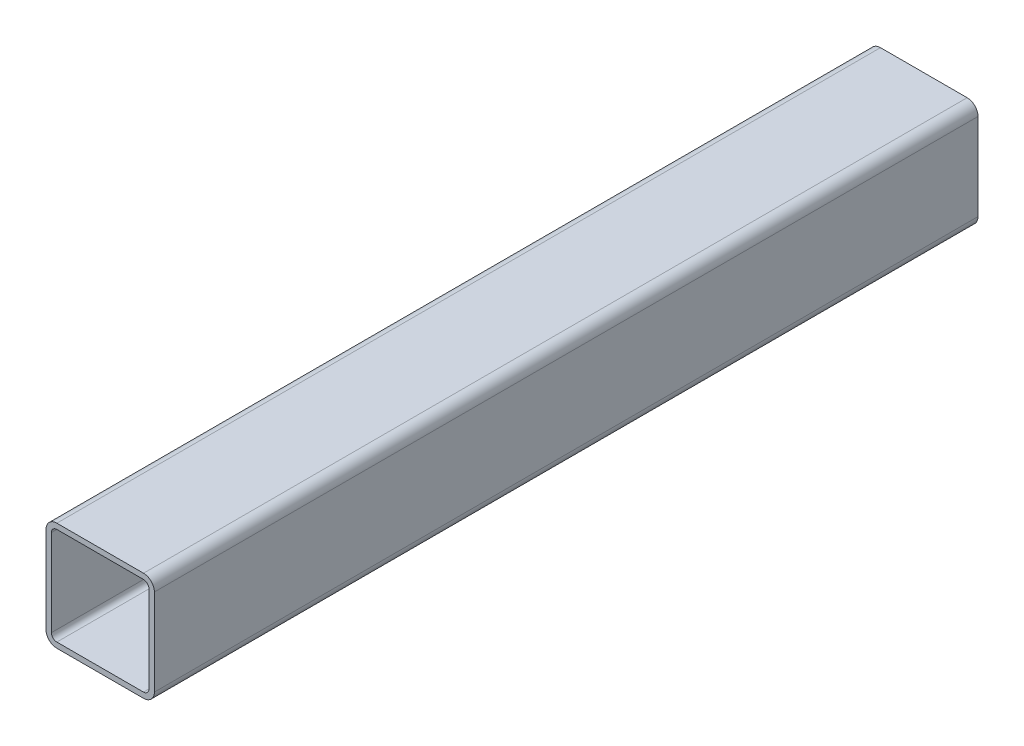
SolidWorks part; units mm, degrees
ref_plane "Front Plane" through (0, 0, 0) normal (0, 0, 1) x (1, 0, 0)
ref_plane "Top Plane" through (0, 0, 0) normal (0, 1, 0) x (1, 0, 0)
ref_plane "Right Plane" through (0, 0, 0) normal (1, 0, 0) x (0, 0, -1)
sketch "Sketch1" plane through (0, 0, 0) normal (0, 0, 1) x (1, 0, 0)
  line L0 (-40, 45) -> (40, 45)
  line L1 (-40, -50) -> (40, -50)
  line L2 (-50, -40) -> (-50, 40)
  line L3 (-40, 50) -> (40, 50)
  line L4 (50, -40) -> (50, 40)
  line L5 (-50, -50) -> (50, 50) construction
  line L6 (-50, 50) -> (50, -50) construction
  line L7 (45, -40) -> (45, 40)
  line L8 (-40, -45) -> (40, -45)
  line L9 (-45, -40) -> (-45, 40)
  arc A0 (-40, 50) -> (-50, 40) centre (-40, 40) ccw
  arc A1 (-50, -40) -> (-40, -50) centre (-40, -40) ccw
  arc A2 (40, -50) -> (50, -40) centre (40, -40) ccw
  arc A3 (50, 40) -> (40, 50) centre (40, 40) ccw
  arc A4 (45, 40) -> (40, 45) centre (40, 40) ccw
  arc A5 (40, -45) -> (45, -40) centre (40, -40) ccw
  arc A6 (-45, -40) -> (-40, -45) centre (-40, -40) ccw
  arc A7 (-40, 45) -> (-45, 40) centre (-40, 40) ccw
  point P0 (0, 0)
  dimension "D2" = 10
  dimension "D1" = 100
  dimension "D3" = 5
extrude "Boss-Extrude1" add sketch "Sketch1" along normal blind 760
